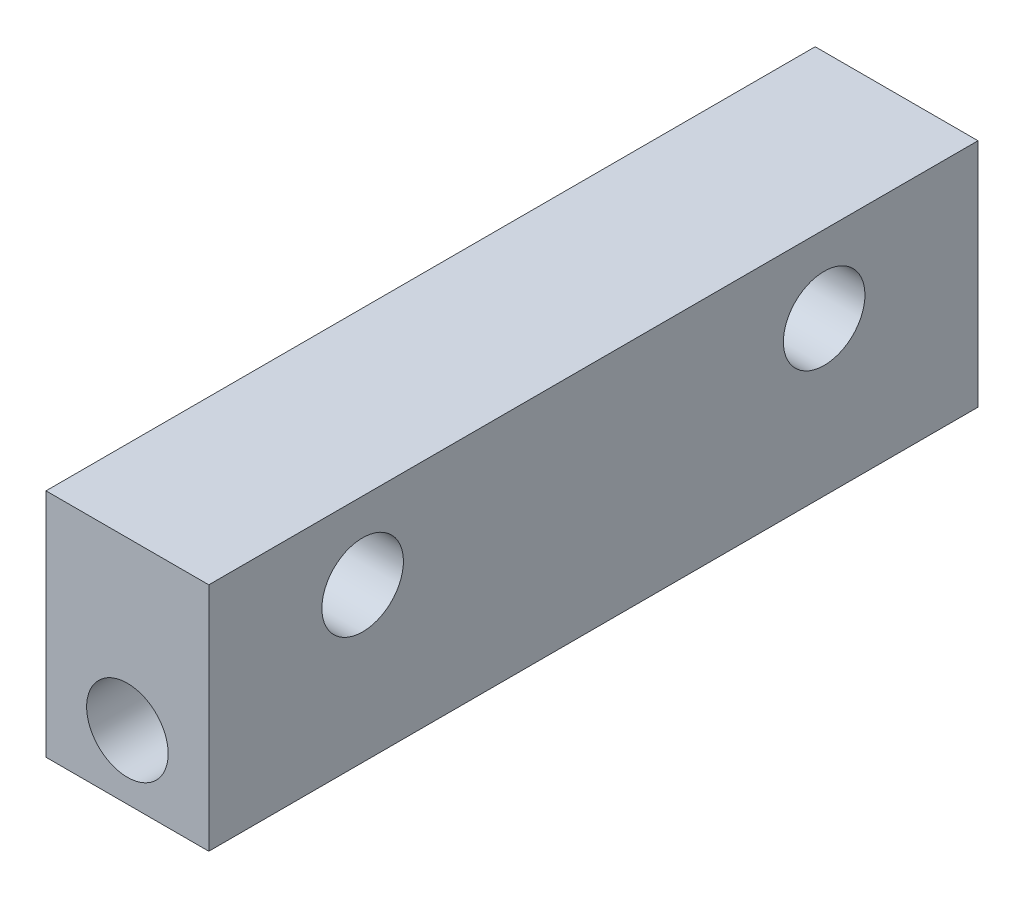
SolidWorks part; units mm, degrees
ref_plane "Front Plane" through (0, 0, 0) normal (0, 0, 1) x (1, 0, 0)
ref_plane "Top Plane" through (0, 0, 0) normal (0, 1, 0) x (1, 0, 0)
ref_plane "Right Plane" through (0, 0, 0) normal (1, 0, 0) x (0, 0, -1)
sketch "Sketch1" plane through (0, 0, 0) normal (0, 0, 1) x (1, 0, 0)
  line L1 (0, 0) -> (6.35, 0)
  line L2 (0, 0) -> (0, -9)
  line L3 (0, -9) -> (6.35, -9)
  line L4 (6.35, 0) -> (6.35, -9)
  circle A0 centre (3.175, -6.5) radius 1.59
  point P7 (3.175, 0)
  dimension "D3" = 3.18
  dimension "D1" = 9
  dimension "D2" = 6.35
  dimension "D4" = 6.5
extrude "Boss-Extrude1" add sketch "Sketch1" along normal blind 30
sketch "Sketch2" plane through (0, 0, 0) normal (1, 0, 0) x (0, 0, -1)
  line L0 (-30, 0) -> (0, 0) construction
  line L3 (-30, -9) -> (-30, 0) construction
  line L4 (-24, -3) -> (-6, -3) construction
  circle A0 centre (-24, -3) radius 1.59
  circle A1 centre (-6, -3) radius 1.59
  dimension "D1" = 3.18
  dimension "D2" = 3
  dimension "D4" = 18
  dimension "D3" = 6
extrude "Cut-Extrude1" cut sketch "Sketch2" along normal blind 30
equation "\"D3@Sketch2\"=(30-\"D4@Sketch2\")/2"
